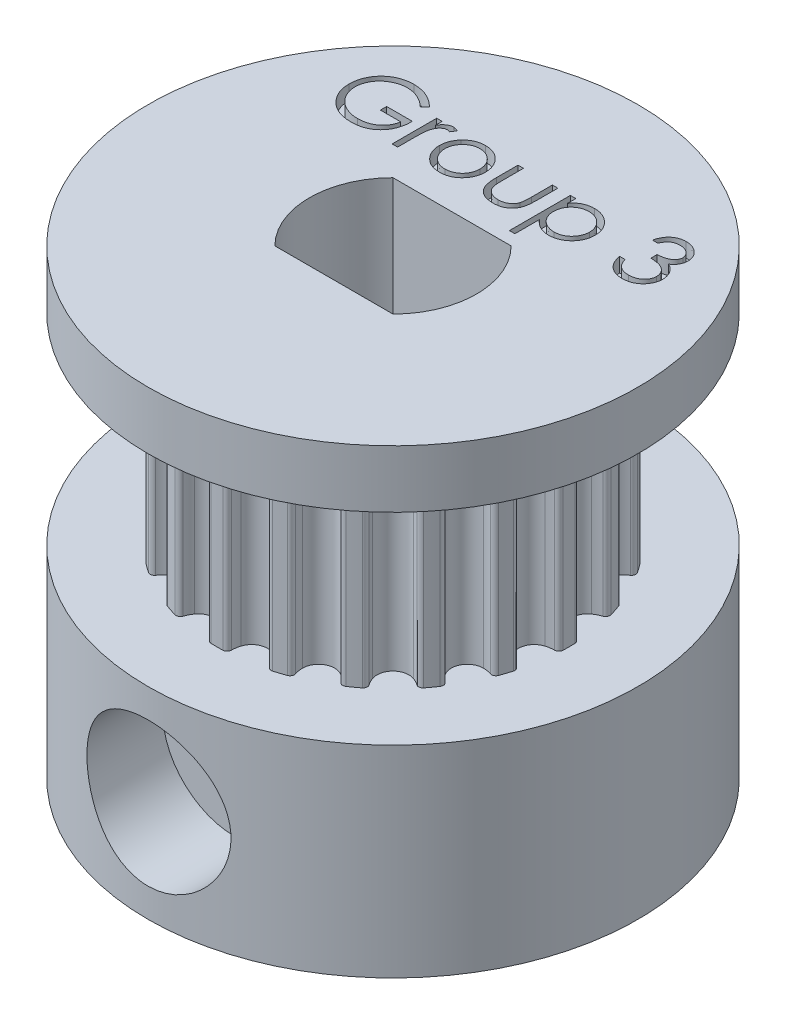
SolidWorks part; units mm, degrees
other "Markup1"
sketch "Sketch11" plane through (-10, 5.5, 10) normal (-0.2341, 0.0958, 0.9675) x (0.972, 0, 0.2351)
sketch "Sketch12" plane through (-9.5, 5.5, 9.5) normal (-0.2341, 0.0958, 0.9675) x (0.972, 0, 0.2351)
sketch "Sketch13" plane through (-9.5, 5.5, 9.5) normal (-0.2341, 0.0958, 0.9675) x (0.972, 0, 0.2351)
sketch "Sketch14" plane through (-8.5, 5.5, 8.5) normal (-0.2341, 0.0958, 0.9675) x (0.972, 0, 0.2351)
sketch "Sketch15" plane through (-8.5, 5.5, 8.5) normal (-0.2341, 0.0958, 0.9675) x (0.972, 0, 0.2351)
sketch "Sketch16" plane through (-8.5, 5.5, 8.5) normal (-0.2341, 0.0958, 0.9675) x (0.972, 0, 0.2351)
sketch "Sketch17" plane through (-8.5, 5.5, 8.5) normal (-0.2341, 0.0958, 0.9675) x (0.972, 0, 0.2351)
sketch "Sketch18" plane through (-8.5, 5.5, 8.5) normal (-0.2341, 0.0958, 0.9675) x (0.972, 0, 0.2351)
sketch "Sketch21" plane through (-8.5, 5.5, 8.5) normal (-0.2341, 0.0958, 0.9675) x (0.972, 0, 0.2351)
sketch "Sketch22" plane through (-8.5, 5.5, 8.5) normal (-0.2341, 0.0958, 0.9675) x (0.972, 0, 0.2351)
ref_plane "Front Plane" through (0, 0, 0) normal (0, 0, 1) x (1, 0, 0)
ref_plane "Top Plane" through (0, 0, 0) normal (0, 1, 0) x (1, 0, 0)
ref_plane "Right Plane" through (0, 0, 0) normal (1, 0, 0) x (0, 0, -1)
sketch "Sketch1" plane through (0, 0, 0) normal (0, 1, 0) x (1, 0, 0)
  line L0 (0, 0) -> (0, 6.3662) construction
  line L2 (0, 0) -> (0.9236, 5.8314) construction
  line L3 (0, 0) -> (1.4053, 6.2092) construction
  line L4 (1.3492, 5.9614) -> (1.2615, 5.4076) construction
  circle A0 centre (0, 0) radius 6.3662
  arc A1 (0.3928, 5.6692) -> (0.8368, 5.2832) centre (0.9236, 5.8314) ccw
  arc A2 (0.3492, 5.9592) -> (0.2042, 6.1088) centre (0.1992, 5.9589) ccw
  arc A3 (0.3492, 5.9592) -> (0.3928, 5.6692) centre (1.3492, 5.9614) ccw
  arc A4 (-0.3928, 5.6692) -> (-0.8368, 5.2832) centre (-0.9236, 5.8314) cw
  arc A5 (0.2042, 6.1088) -> (-0.2042, 6.1088) centre (0, 0) ccw
  arc A6 (-0.3492, 5.9592) -> (-0.3928, 5.6692) centre (-1.3492, 5.9614) cw
  arc A7 (-0.3492, 5.9592) -> (-0.2042, 6.1088) centre (-0.1992, 5.9589) cw
  arc A8 (1.3783, 5.5132) -> (0.8368, 5.2832) centre (0.9236, 5.8314) cw
  arc A9 (1.5094, 5.7754) -> (1.3783, 5.5132) centre (0.559, 6.0866) cw
  arc A10 (1.5094, 5.7754) -> (1.6935, 5.8729) centre (1.652, 5.7288) cw
  arc A11 (2.0819, 5.7467) -> (1.6935, 5.8729) centre (0, 0) ccw
  arc A12 (2.1736, 5.5596) -> (2.0819, 5.7467) centre (2.0308, 5.6057) ccw
  arc A13 (2.1736, 5.5596) -> (2.1255, 5.2704) centre (3.1253, 5.2527) ccw
  arc A14 (2.1255, 5.2704) -> (2.4284, 4.7661) centre (2.6804, 5.2606) ccw
  arc A15 (3.0145, 4.8174) -> (2.4284, 4.7661) centre (2.6804, 5.2606) cw
  arc A16 (3.2202, 5.0263) -> (3.0145, 4.8174) centre (2.4125, 5.6159) cw
  arc A17 (3.2202, 5.0263) -> (3.4255, 5.0621) centre (3.3414, 4.9379) cw
  arc A18 (3.7559, 4.8221) -> (3.4255, 5.0621) centre (0, 0) ccw
  arc A19 (3.7852, 4.6159) -> (3.7559, 4.8221) centre (3.6637, 4.7037) ccw
  arc A20 (3.7852, 4.6159) -> (3.6501, 4.3556) centre (4.5956, 4.0299) ccw
  arc A21 (3.6501, 4.3556) -> (3.7824, 3.7824) centre (4.1748, 4.1748) ccw
  arc A22 (4.3556, 3.6501) -> (3.7824, 3.7824) centre (4.1748, 4.1748) cw
  arc A23 (4.6159, 3.7852) -> (4.3556, 3.6501) centre (4.0299, 4.5956) cw
  arc A24 (4.6159, 3.7852) -> (4.8221, 3.7559) centre (4.7037, 3.6637) cw
  arc A25 (5.0621, 3.4255) -> (4.8221, 3.7559) centre (0, 0) ccw
  arc A26 (5.0263, 3.2202) -> (5.0621, 3.4255) centre (4.9379, 3.3414) ccw
  arc A27 (5.0263, 3.2202) -> (4.8174, 3.0145) centre (5.6159, 2.4125) ccw
  arc A28 (4.8174, 3.0145) -> (4.7661, 2.4284) centre (5.2606, 2.6804) ccw
  arc A29 (5.2704, 2.1255) -> (4.7661, 2.4284) centre (5.2606, 2.6804) cw
  arc A30 (5.5596, 2.1736) -> (5.2704, 2.1255) centre (5.2527, 3.1253) cw
  arc A31 (5.5596, 2.1736) -> (5.7467, 2.0819) centre (5.6057, 2.0308) cw
  arc A32 (5.8729, 1.6935) -> (5.7467, 2.0819) centre (0, 0) ccw
  arc A33 (5.7754, 1.5094) -> (5.8729, 1.6935) centre (5.7288, 1.652) ccw
  arc A34 (5.7754, 1.5094) -> (5.5132, 1.3783) centre (6.0866, 0.559) ccw
  arc A35 (5.5132, 1.3783) -> (5.2832, 0.8368) centre (5.8314, 0.9236) ccw
  arc A36 (5.6692, 0.3928) -> (5.2832, 0.8368) centre (5.8314, 0.9236) cw
  arc A37 (5.9592, 0.3492) -> (5.6692, 0.3928) centre (5.9614, 1.3492) cw
  arc A38 (5.9592, 0.3492) -> (6.1088, 0.2042) centre (5.9589, 0.1992) cw
  arc A39 (6.1088, -0.2042) -> (6.1088, 0.2042) centre (0, 0) ccw
  arc A40 (5.9592, -0.3492) -> (6.1088, -0.2042) centre (5.9589, -0.1992) ccw
  arc A41 (5.9592, -0.3492) -> (5.6692, -0.3928) centre (5.9614, -1.3492) ccw
  arc A42 (5.6692, -0.3928) -> (5.2832, -0.8368) centre (5.8314, -0.9236) ccw
  arc A43 (5.5132, -1.3783) -> (5.2832, -0.8368) centre (5.8314, -0.9236) cw
  arc A44 (5.7754, -1.5094) -> (5.5132, -1.3783) centre (6.0866, -0.559) cw
  arc A45 (5.7754, -1.5094) -> (5.8729, -1.6935) centre (5.7288, -1.652) cw
  arc A46 (5.7467, -2.0819) -> (5.8729, -1.6935) centre (0, 0) ccw
  arc A47 (5.5596, -2.1736) -> (5.7467, -2.0819) centre (5.6057, -2.0308) ccw
  arc A48 (5.5596, -2.1736) -> (5.2704, -2.1255) centre (5.2527, -3.1253) ccw
  arc A49 (5.2704, -2.1255) -> (4.7661, -2.4284) centre (5.2606, -2.6804) ccw
  arc A50 (4.8174, -3.0145) -> (4.7661, -2.4284) centre (5.2606, -2.6804) cw
  arc A51 (5.0263, -3.2202) -> (4.8174, -3.0145) centre (5.6159, -2.4125) cw
  arc A52 (5.0263, -3.2202) -> (5.0621, -3.4255) centre (4.9379, -3.3414) cw
  arc A53 (4.8221, -3.7559) -> (5.0621, -3.4255) centre (0, 0) ccw
  arc A54 (4.6159, -3.7852) -> (4.8221, -3.7559) centre (4.7037, -3.6637) ccw
  arc A55 (4.6159, -3.7852) -> (4.3556, -3.6501) centre (4.0299, -4.5956) ccw
  arc A56 (4.3556, -3.6501) -> (3.7824, -3.7824) centre (4.1748, -4.1748) ccw
  arc A57 (3.6501, -4.3556) -> (3.7824, -3.7824) centre (4.1748, -4.1748) cw
  arc A58 (3.7852, -4.6159) -> (3.6501, -4.3556) centre (4.5956, -4.0299) cw
  arc A59 (3.7852, -4.6159) -> (3.7559, -4.8221) centre (3.6637, -4.7037) cw
  arc A60 (3.4255, -5.0621) -> (3.7559, -4.8221) centre (0, 0) ccw
  arc A61 (3.2202, -5.0263) -> (3.4255, -5.0621) centre (3.3414, -4.9379) ccw
  arc A62 (3.2202, -5.0263) -> (3.0145, -4.8174) centre (2.4125, -5.6159) ccw
  arc A63 (3.0145, -4.8174) -> (2.4284, -4.7661) centre (2.6804, -5.2606) ccw
  arc A64 (2.1255, -5.2704) -> (2.4284, -4.7661) centre (2.6804, -5.2606) cw
  arc A65 (2.1736, -5.5596) -> (2.1255, -5.2704) centre (3.1253, -5.2527) cw
  arc A66 (2.1736, -5.5596) -> (2.0819, -5.7467) centre (2.0308, -5.6057) cw
  arc A67 (1.6935, -5.8729) -> (2.0819, -5.7467) centre (0, 0) ccw
  arc A68 (1.5094, -5.7754) -> (1.6935, -5.8729) centre (1.652, -5.7288) ccw
  arc A69 (1.5094, -5.7754) -> (1.3783, -5.5132) centre (0.559, -6.0866) ccw
  arc A70 (1.3783, -5.5132) -> (0.8368, -5.2832) centre (0.9236, -5.8314) ccw
  arc A71 (0.3928, -5.6692) -> (0.8368, -5.2832) centre (0.9236, -5.8314) cw
  arc A72 (0.3492, -5.9592) -> (0.3928, -5.6692) centre (1.3492, -5.9614) cw
  arc A73 (0.3492, -5.9592) -> (0.2042, -6.1088) centre (0.1992, -5.9589) cw
  arc A74 (-0.2042, -6.1088) -> (0.2042, -6.1088) centre (0, 0) ccw
  arc A75 (-0.3492, -5.9592) -> (-0.2042, -6.1088) centre (-0.1992, -5.9589) ccw
  arc A76 (-0.3492, -5.9592) -> (-0.3928, -5.6692) centre (-1.3492, -5.9614) ccw
  arc A77 (-0.3928, -5.6692) -> (-0.8368, -5.2832) centre (-0.9236, -5.8314) ccw
  arc A78 (-1.3783, -5.5132) -> (-0.8368, -5.2832) centre (-0.9236, -5.8314) cw
  arc A79 (-1.5094, -5.7754) -> (-1.3783, -5.5132) centre (-0.559, -6.0866) cw
  arc A80 (-1.5094, -5.7754) -> (-1.6935, -5.8729) centre (-1.652, -5.7288) cw
  arc A81 (-2.0819, -5.7467) -> (-1.6935, -5.8729) centre (0, 0) ccw
  arc A82 (-2.1736, -5.5596) -> (-2.0819, -5.7467) centre (-2.0308, -5.6057) ccw
  arc A83 (-2.1736, -5.5596) -> (-2.1255, -5.2704) centre (-3.1253, -5.2527) ccw
  arc A84 (-2.1255, -5.2704) -> (-2.4284, -4.7661) centre (-2.6804, -5.2606) ccw
  arc A85 (-3.0145, -4.8174) -> (-2.4284, -4.7661) centre (-2.6804, -5.2606) cw
  arc A86 (-3.2202, -5.0263) -> (-3.0145, -4.8174) centre (-2.4125, -5.6159) cw
  arc A87 (-3.2202, -5.0263) -> (-3.4255, -5.0621) centre (-3.3414, -4.9379) cw
  arc A88 (-3.7559, -4.8221) -> (-3.4255, -5.0621) centre (0, 0) ccw
  arc A89 (-3.7852, -4.6159) -> (-3.7559, -4.8221) centre (-3.6637, -4.7037) ccw
  arc A90 (-3.7852, -4.6159) -> (-3.6501, -4.3556) centre (-4.5956, -4.0299) ccw
  arc A91 (-3.6501, -4.3556) -> (-3.7824, -3.7824) centre (-4.1748, -4.1748) ccw
  arc A92 (-4.3556, -3.6501) -> (-3.7824, -3.7824) centre (-4.1748, -4.1748) cw
  arc A93 (-4.6159, -3.7852) -> (-4.3556, -3.6501) centre (-4.0299, -4.5956) cw
  arc A94 (-4.6159, -3.7852) -> (-4.8221, -3.7559) centre (-4.7037, -3.6637) cw
  arc A95 (-5.0621, -3.4255) -> (-4.8221, -3.7559) centre (0, 0) ccw
  arc A96 (-5.0263, -3.2202) -> (-5.0621, -3.4255) centre (-4.9379, -3.3414) ccw
  arc A97 (-5.0263, -3.2202) -> (-4.8174, -3.0145) centre (-5.6159, -2.4125) ccw
  arc A98 (-4.8174, -3.0145) -> (-4.7661, -2.4284) centre (-5.2606, -2.6804) ccw
  arc A99 (-5.2704, -2.1255) -> (-4.7661, -2.4284) centre (-5.2606, -2.6804) cw
  arc A100 (-5.5596, -2.1736) -> (-5.2704, -2.1255) centre (-5.2527, -3.1253) cw
  arc A101 (-5.5596, -2.1736) -> (-5.7467, -2.0819) centre (-5.6057, -2.0308) cw
  arc A102 (-5.8729, -1.6935) -> (-5.7467, -2.0819) centre (0, 0) ccw
  arc A103 (-5.7754, -1.5094) -> (-5.8729, -1.6935) centre (-5.7288, -1.652) ccw
  arc A104 (-5.7754, -1.5094) -> (-5.5132, -1.3783) centre (-6.0866, -0.559) ccw
  arc A105 (-5.5132, -1.3783) -> (-5.2832, -0.8368) centre (-5.8314, -0.9236) ccw
  arc A106 (-5.6692, -0.3928) -> (-5.2832, -0.8368) centre (-5.8314, -0.9236) cw
  arc A107 (-5.9592, -0.3492) -> (-5.6692, -0.3928) centre (-5.9614, -1.3492) cw
  arc A108 (-5.9592, -0.3492) -> (-6.1088, -0.2042) centre (-5.9589, -0.1992) cw
  arc A109 (-6.1088, 0.2042) -> (-6.1088, -0.2042) centre (0, 0) ccw
  arc A110 (-5.9592, 0.3492) -> (-6.1088, 0.2042) centre (-5.9589, 0.1992) ccw
  arc A111 (-5.9592, 0.3492) -> (-5.6692, 0.3928) centre (-5.9614, 1.3492) ccw
  arc A112 (-5.6692, 0.3928) -> (-5.2832, 0.8368) centre (-5.8314, 0.9236) ccw
  arc A113 (-5.5132, 1.3783) -> (-5.2832, 0.8368) centre (-5.8314, 0.9236) cw
  arc A114 (-5.7754, 1.5094) -> (-5.5132, 1.3783) centre (-6.0866, 0.559) cw
  arc A115 (-5.7754, 1.5094) -> (-5.8729, 1.6935) centre (-5.7288, 1.652) cw
  arc A116 (-5.7467, 2.0819) -> (-5.8729, 1.6935) centre (0, 0) ccw
  arc A117 (-5.5596, 2.1736) -> (-5.7467, 2.0819) centre (-5.6057, 2.0308) ccw
  arc A118 (-5.5596, 2.1736) -> (-5.2704, 2.1255) centre (-5.2527, 3.1253) ccw
  arc A119 (-5.2704, 2.1255) -> (-4.7661, 2.4284) centre (-5.2606, 2.6804) ccw
  arc A120 (-4.8174, 3.0145) -> (-4.7661, 2.4284) centre (-5.2606, 2.6804) cw
  arc A121 (-5.0263, 3.2202) -> (-4.8174, 3.0145) centre (-5.6159, 2.4125) cw
  arc A122 (-5.0263, 3.2202) -> (-5.0621, 3.4255) centre (-4.9379, 3.3414) cw
  arc A123 (-4.8221, 3.7559) -> (-5.0621, 3.4255) centre (0, 0) ccw
  arc A124 (-4.6159, 3.7852) -> (-4.8221, 3.7559) centre (-4.7037, 3.6637) ccw
  arc A125 (-4.6159, 3.7852) -> (-4.3556, 3.6501) centre (-4.0299, 4.5956) ccw
  arc A126 (-4.3556, 3.6501) -> (-3.7824, 3.7824) centre (-4.1748, 4.1748) ccw
  arc A127 (-3.6501, 4.3556) -> (-3.7824, 3.7824) centre (-4.1748, 4.1748) cw
  arc A128 (-3.7852, 4.6159) -> (-3.6501, 4.3556) centre (-4.5956, 4.0299) cw
  arc A129 (-3.7852, 4.6159) -> (-3.7559, 4.8221) centre (-3.6637, 4.7037) cw
  arc A130 (-3.4255, 5.0621) -> (-3.7559, 4.8221) centre (0, 0) ccw
  arc A131 (-3.2202, 5.0263) -> (-3.4255, 5.0621) centre (-3.3414, 4.9379) ccw
  arc A132 (-3.2202, 5.0263) -> (-3.0145, 4.8174) centre (-2.4125, 5.6159) ccw
  arc A133 (-3.0145, 4.8174) -> (-2.4284, 4.7661) centre (-2.6804, 5.2606) ccw
  arc A134 (-2.1255, 5.2704) -> (-2.4284, 4.7661) centre (-2.6804, 5.2606) cw
  arc A135 (-2.1736, 5.5596) -> (-2.1255, 5.2704) centre (-3.1253, 5.2527) cw
  arc A136 (-2.1736, 5.5596) -> (-2.0819, 5.7467) centre (-2.0308, 5.6057) cw
  arc A137 (-1.6935, 5.8729) -> (-2.0819, 5.7467) centre (0, 0) ccw
  arc A138 (-1.5094, 5.7754) -> (-1.6935, 5.8729) centre (-1.652, 5.7288) ccw
  arc A139 (-1.5094, 5.7754) -> (-1.3783, 5.5132) centre (-0.559, 6.0866) ccw
  arc A140 (-1.3783, 5.5132) -> (-0.8368, 5.2832) centre (-0.9236, 5.8314) ccw
  point P4 (0, 6.1122)
  point P11 (0, 6.3662)
  point P67 (0, 0)
  dimension "D1" = 12.7324
  dimension "D3" = 1
  dimension "D4" = 0.555
  dimension "D2" = 0.15
  dimension "D5" = 0.4
  dimension "D8" = 0.254
  dimension "D7" = 9
  dimension "D6" = 0.254
  dimension "D9" = 20
extrude "Gear" add sketch "Sketch1" along normal mid plane 7 contours A140 A139 A138 A137 A136 A135 A134 A133 A132 A131 A130 A129 A128 A127 A126 A125 A124 A123 A122 A121 A120 A119 A118 A117 A116 A115 A114 A113 A112 A111 A110 A109 A108 A107 A106 A105 A104 A103 A102 A101 A100 A99 A98 A97 A96 A95 A94 A93 A92 A91 A90 region at (0, 0, 0)
sketch "Sketch2" plane through (0, -3.5, 0) normal (0, -1, 0) x (1, 0, 0)
  line L0 (-11.7249, 0) -> (11.7249, 0) construction
  line L1 (-1.9666, 1.85) -> (1.9666, 1.85)
  line L2 (-1.9666, -1.85) -> (1.9666, -1.85)
  line L3 (-2.0512, -2.05) -> (2.0512, -2.05)
  line L4 (-2.0512, 2.05) -> (2.0512, 2.05)
  arc A0 (-1.9666, 1.85) -> (-1.9666, -1.85) centre (0, 0) ccw
  arc A1 (1.9666, -1.85) -> (1.9666, 1.85) centre (0, 0) ccw
  arc A2 (2.0512, -2.05) -> (2.0512, 2.05) centre (0, 0) ccw
  arc A3 (-2.0512, 2.05) -> (-2.0512, -2.05) centre (0, 0) ccw
  circle A4 centre (0, 0) radius 8.5
  point P4 (0, 0)
  dimension "D2" = 5.4
  dimension "D4" = 17
  dimension "D1" = 3.7
  dimension "D3" = 0.2
extrude "Base" add sketch "Sketch2" along normal blind 7 contours A4 L0 A3 L4 A2 | L0 A4 A2 L3 A3 region at (0, -3.5, 3.8849) region at (0, -3.5, -3.8849)
sketch "Sketch3" plane through (0, 0, 0) normal (0, 0, 1) x (1, 0, 0)
  line L0 (0, 0) -> (0, -7) construction
  line L1 (0, -10.06) -> (2.65, -8.53)
  line L2 (2.65, -8.53) -> (2.65, -5.47)
  line L3 (2.65, -5.47) -> (0, -3.94)
  line L4 (0, -3.94) -> (-2.65, -5.47)
  line L5 (-2.65, -5.47) -> (-2.65, -8.53)
  line L6 (-2.65, -8.53) -> (0, -10.06)
  line L7 (-2.65, -8.53) -> (-2.65, -10.5)
  line L8 (-8.5, -10.5) -> (8.5, -10.5) construction
  line L9 (-2.65, -10.5) -> (2.65, -10.5)
  line L10 (2.65, -10.5) -> (2.65, -8.53)
  circle A0 centre (0, -7) radius 2.65 construction
  dimension "D1" = 5.3
  dimension "D2" = 7
extrude "Nut Passthrough" cut sketch "Sketch3" along normal blind 4.2 contours L9 L10 L1 L6 L7 | L5 L6 L1 L2 L3 L4 region at (0, -7, 0) region at (1.3533, -9.3439, 0)
sketch "Sketch9" plane through (0, 3.5, 0) normal (0, 1, 0) x (1, 0, 0)
  circle A0 centre (0, 0) radius 8.5
  dimension "D1" = 17
extrude "Top" add sketch "Sketch9" along normal blind 2
extrude "Shaft Hole" cut sketch "Sketch2<4>" against normal through all contours A0 L0 A1 L1 | L0 A0 L2 A1 | L0 A3 L3 A2 A1 L2 A0 | A3 L0 A0 L1 A1 A2 L4 region at (-2.6226, -3.5, 1.0859) region at (-2.8, -3.5, -0.0615) region at (0, -3.5, 0.8808) region at (0, -3.5, -0.8808)
sketch "Sketch2<4>" plane through (0, -3.5, 0) normal (0, -1, 0) x (1, 0, 0) same geometry as "Sketch2"
sketch "Sketch10" plane through (0, 0, 0) normal (0, 0, 1) x (1, 0, 0)
  circle A0 centre (0, -7) radius 1.4
  circle A1 centre (0, -7) radius 2.5
  dimension "D1" = 2.8
  dimension "D2" = 5
extrude "Screw Hole" cut sketch "Sketch10" along normal through all contours A0 region at (0, -7, 0)
extrude "Screw Counterbore" cut sketch "Sketch10<3>" along normal through all from offset 5.5
sketch "Sketch10<3>" plane through (0, 0, 0) normal (0, 0, 1) x (1, 0, 0) same geometry as "Sketch10"
sketch "Sketch20" plane through (0, 5.5, 0) normal (0, 1, 0) x (1, 0, 0)
  line L0 (-7.4515, 3.05) -> (7.4515, 3.05) construction
  line L1 (-2.0512, 2.05) -> (2.0512, 2.05) construction
  line L2 (-2.65, 0) -> (2.65, 0) construction
  text T0 "Group 3" font "Century Gothic" height in points 8
  point P6 (0, 3.05)
  dimension "D1" = 1
extrude "Cut-Extrude2" cut sketch "Sketch20" against normal blind 0.5
equation "\"D1@Sketch1\"=\"pd\""
equation "\"teethNum\"= 20"
equation "\"pitch\"= 2mm"
equation "\"pd\"= \"teethNum\" * \"pitch\" / PI"
equation "\"D9@Sketch1\"=\"teethNum\""
equation "\"outerDia\"= 17"
equation "\"D4@Sketch2\"=\"outerDia\""
equation "\"D1@Sketch9\"=\"outerDia\""
equation "\"D7@Sketch1\"=180/ \"teethNum\""
